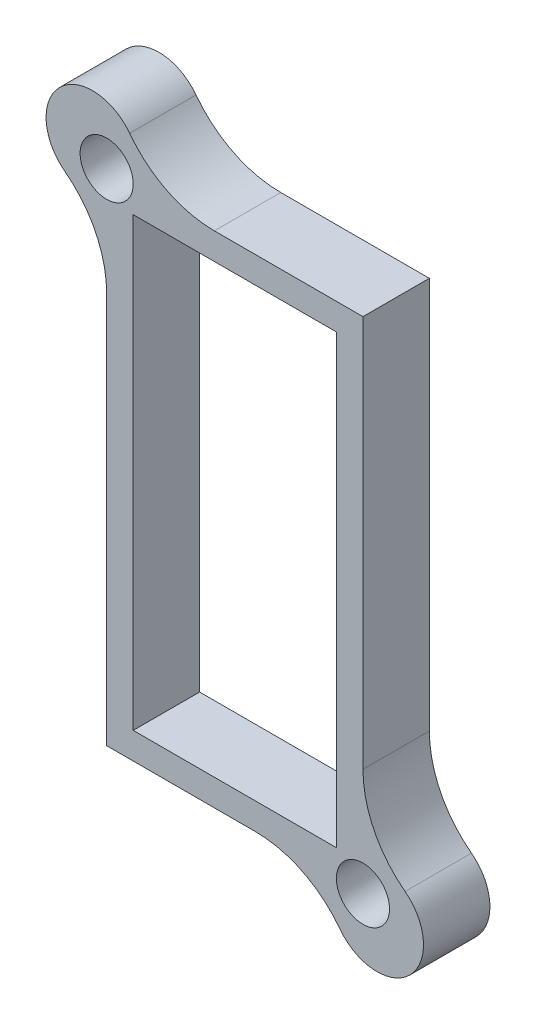
SolidWorks part; units mm, degrees
note: The reader was unsure of these and kept them because the rebuilt part matched: shared geometry of "Sketch4<2>".
ref_plane "Front Plane" through (0, 0, 0) normal (0, 0, 1) x (1, 0, 0)
ref_plane "Top Plane" through (0, 0, 0) normal (0, 1, 0) x (1, 0, 0)
ref_plane "Right Plane" through (0, 0, 0) normal (1, 0, 0) x (0, 0, -1)
other "Configuration Table"
sketch "Sketch3" plane through (0, 0, 0) normal (0, 0, 1) x (1, 0, 0)
  line L0 (-8.1445, -24) -> (66.8555, -24) construction
  line L1 (29.3555, -4) -> (29.3555, -44) construction
  line L2 (10.6055, -24) -> (-8.1445, -24)
  line L3 (6.7805, -32.4083) -> (14.4305, -32.4083)
  line L4 (6.7805, -32.4083) -> (6.7805, -15.5917)
  line L5 (6.7805, -15.5917) -> (14.4305, -15.5917)
  line L6 (68.8555, -46) -> (68.8555, -26)
  line L7 (66.8555, -24) -> (66.8555, -4)
  line L8 (66.8555, -4) -> (-8.1445, -4)
  line L9 (-8.1445, -4) -> (-8.1445, -44)
  line L10 (-8.1445, -44) -> (38.8555, -44)
  line L11 (40.8555, -46) -> (68.8555, -46)
  line L12 (68.8555, -46) -> (68.8555, -26)
  line L13 (66.8555, -24) -> (66.8555, -4)
  line L14 (66.8555, -4) -> (-8.1445, -4)
  line L15 (-8.1445, -4) -> (-8.1445, -44)
  line L16 (-8.1445, -44) -> (38.8555, -44)
  line L17 (40.8555, -46) -> (68.8555, -46)
  line L18 (14.4305, -32.4083) -> (14.4305, -15.5917)
  line L19 (6.7805, -32.4083) -> (14.4305, -15.5917) construction
  line L20 (6.7805, -15.5917) -> (14.4305, -32.4083) construction
  arc A2 (66.8555, -24) -> (68.8555, -26) centre (68.8555, -24) ccw
  arc A3 (40.8555, -46) -> (38.8555, -44) centre (38.8555, -46) ccw
  arc A4 (66.8555, -24) -> (68.8555, -26) centre (68.8555, -24) ccw
  arc A5 (40.8555, -46) -> (38.8555, -44) centre (38.8555, -46) ccw
  point P11 (10.6055, -24)
  dimension "D2" = 7.65
  dimension "D3" = 16.8167
  dimension "D4" = 75
  dimension "D5" = 18.75
  dimension "D1" = 0
extrude "Extrude-Thin1" add sketch "Sketch3" along normal blind 2.5 thin
sketch "Sketch4" plane through (0, 0, 2.5) normal (0, 0, 1) x (1, 0, 0)
  line L0 (15.4305, -33.4083) -> (15.9608, -33.9387) construction
  line L2 (15.4305, -33.4083) -> (16.4305, -33.4083) construction
  line L3 (5.7805, -24) -> (15.4305, -24) construction
  line L4 (5.7805, -33.4083) -> (5.7805, -14.5917) construction
  line L5 (15.4305, -33.4083) -> (15.4305, -14.5917) construction
  line L6 (10.6055, -14.5917) -> (10.6055, -33.4083) construction
  line L7 (5.7805, -14.5917) -> (15.4305, -14.5917) construction
  line L8 (5.7805, -33.4083) -> (15.4305, -33.4083) construction
  circle A2 centre (5.7805, -14.5917) radius 1
  circle A3 centre (15.4305, -33.4083) radius 1
  circle A4 centre (15.9608, -33.9387) radius 1.75
  circle A5 centre (5.2502, -33.9387) radius 1.75 construction
  circle A6 centre (5.2502, -14.0613) radius 1.75
  line M1 (5.7805, -33.4083) -> (15.4305, -33.4083)
  line M2 (15.4305, -33.4083) -> (15.4305, -14.5917)
  line M3 (15.4305, -14.5917) -> (5.7805, -14.5917)
  line M4 (5.7805, -14.5917) -> (5.7805, -33.4083)
  dimension "D1" = 2
  dimension "D2" = 2
  dimension "D3" = 3.5
  dimension "D4" = 45
extrude "Boss-Extrude2" add sketch "Sketch4" against normal up to surface (2.5 mm away) contours A6 A2 M3 M4 | A4 A3 M1 M2 up to face at (10.6055, -24, 0)
extrude "Cut-Extrude1" cut sketch "Sketch4<2>" against normal up to surface (2.5 mm away) contours A2 M4 M3 | A3 M2 M1
sketch "Sketch4<2>" plane through (0, 0, 2.5) normal (0, 0, 1) x (1, 0, 0) same geometry as "Sketch4"
fillet "Fillet1" radius 4 4 edges at (14.2931, -33.4083, 1.25) (15.4305, -32.271, 1.25) (6.9179, -14.5917, 1.25) (5.7805, -15.729, 1.25)
equation "\"D2@Sketch3\"= 7.5 + \"C\""
equation "\"C\"= 0.15'Clearance Gap"
equation "\"D3@Sketch3\"=16.66667+\"C\""
equation "\"F\"=4"
equation "\"D1@Fillet1\"=\"F\""
